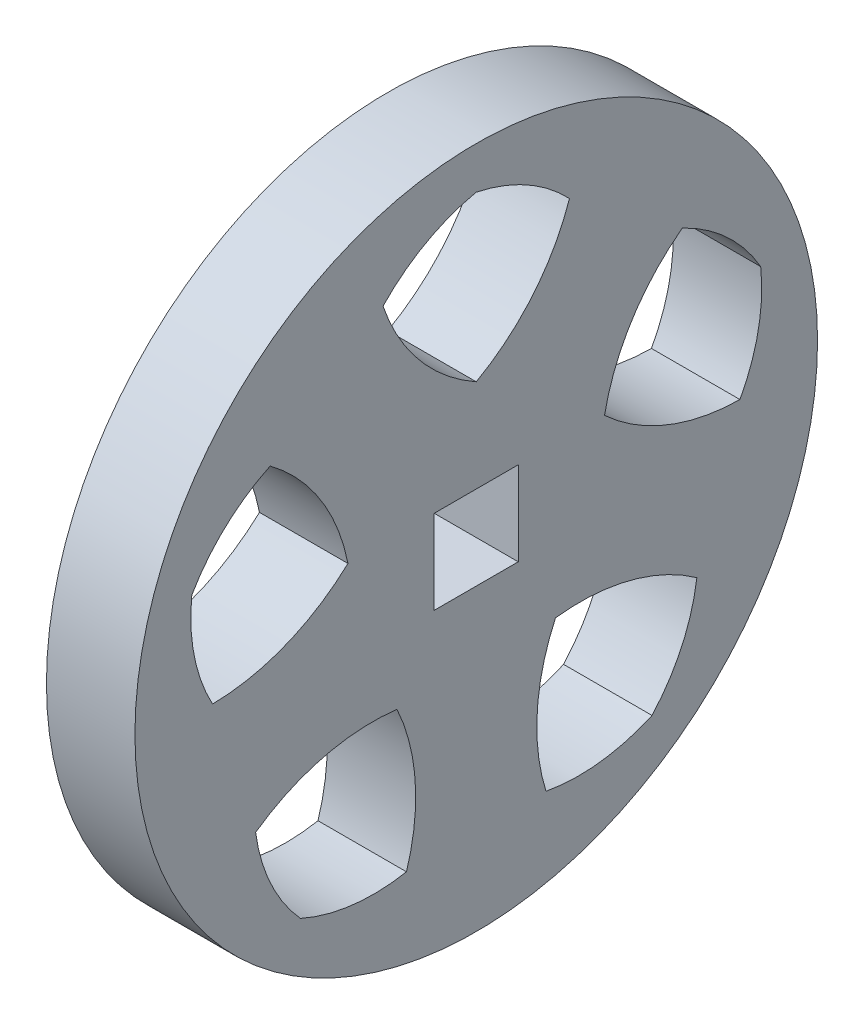
SolidWorks part; units mm, degrees
ref_plane "Front Plane" through (0, 0, 0) normal (0, 0, 1) x (1, 0, 0)
ref_plane "Top Plane" through (0, 0, 0) normal (0, 1, 0) x (1, 0, 0)
ref_plane "Right Plane" through (0, 0, 0) normal (1, 0, 0) x (0, 0, -1)
sketch "Sketch1" plane through (0, 0, 0) normal (1, 0, 0) x (0, 0, -1)
  circle A0 centre (0, 0) radius 13.5
  dimension "D1" = 27
extrude "Boss-Extrude1" add sketch "Sketch1" along normal blind 3.5
sketch "Sketch2" plane through (0, 0, 0) normal (1, 0, 0) x (0, 0, -1)
  line L0 (0, 0) -> (0, 14.8201) construction
  arc A0 (0, 5.3352) -> (-3.6873, 9.769) centre (3.9038, 12.3319) cw
  arc A1 (-3.6873, 9.769) -> (0, 11.8295) centre (1.4581, 4.8907) cw
  arc A2 (3.6873, 9.769) -> (0, 11.8295) centre (-1.4581, 4.8907) ccw
  arc A3 (0, 5.3352) -> (3.6873, 9.769) centre (-3.9038, 12.3319) ccw
extrude "Cut-Extrude1" cut sketch "Sketch2" along normal up to next
pattern_circular "CirPattern1" count 5 over 360 about axis through (3.5, 0, 0) along (-1, 0, 0) of "Cut-Extrude1" reverse direction yes
sketch "Sketch3" plane through (0, 0, 0) normal (1, 0, 0) x (0, 0, -1)
  line L1 (1.6617, -1.6617) -> (-1.6617, -1.6617)
  line L2 (1.6617, -1.6617) -> (1.6617, 1.6617)
  line L3 (1.6617, 1.6617) -> (-1.6617, 1.6617)
  line L4 (-1.6617, -1.6617) -> (-1.6617, 1.6617)
  line L5 (1.6617, -1.6617) -> (-1.6617, 1.6617) construction
  line L6 (1.6617, 1.6617) -> (-1.6617, -1.6617) construction
  circle A0 centre (0, 0) radius 2.35 construction
  dimension "D1" = 4.7
extrude "Cut-Extrude2" cut sketch "Sketch3" along normal up to next
